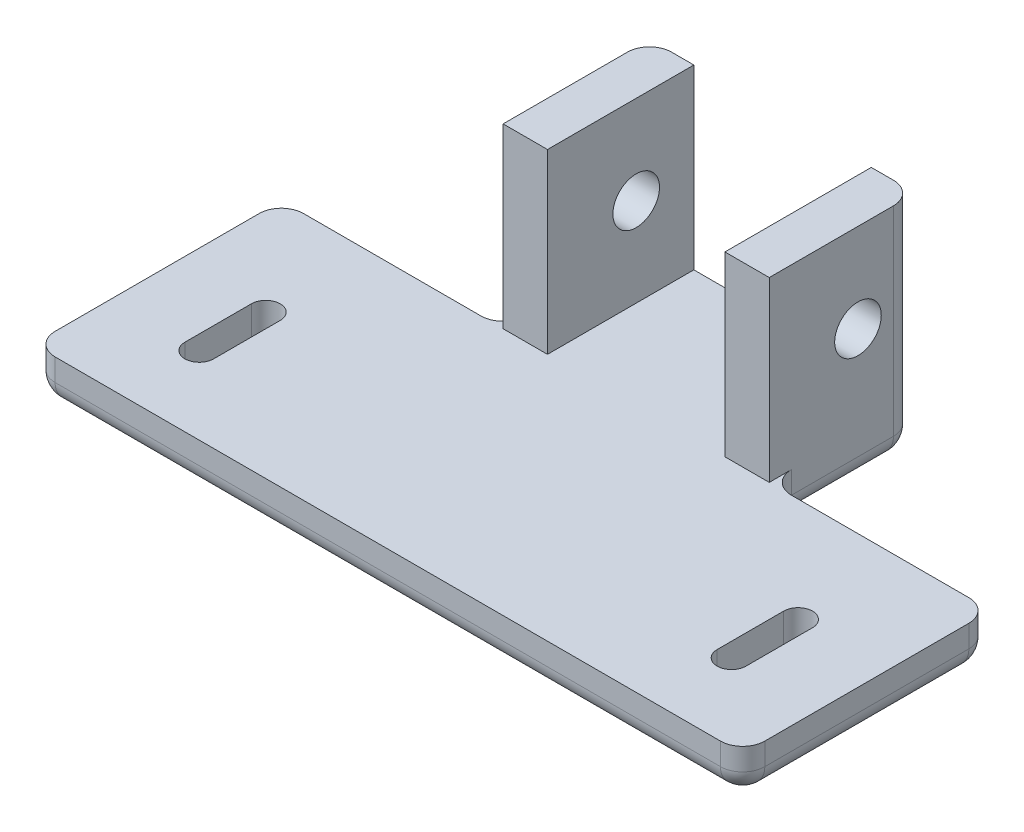
SolidWorks part; units mm, degrees
ref_plane "Front Plane" through (0, 0, 0) normal (0, 0, 1) x (1, 0, 0)
ref_plane "Top Plane" through (0, 0, 0) normal (0, 1, 0) x (1, 0, 0)
ref_plane "Right Plane" through (0, 0, 0) normal (1, 0, 0) x (0, 0, -1)
sketch "Sketch1" plane through (0, 0, 0) normal (1, 0, 0) x (0, 0, -1)
  line L0 (-10, -10) -> (6.5, -10)
  line L5 (-10, 10) -> (6.5, 10)
  line L7 (-10, -15) -> (6.5, -15)
  line L8 (6.5, 10) -> (6.5, -15)
  line L9 (-10, -10) -> (-38, -10)
  line L10 (-38, -10) -> (-38, -15)
  line L11 (-38, -15) -> (-10, -15)
  line L12 (6.5, 10) -> (10, 10) construction
  line L13 (10, 10) -> (10, -15) construction
  line L14 (10, -15) -> (6.5, -15) construction
  line L15 (-10, -10) -> (-10, 10)
  line L16 (-10, -15) -> (-10, -10)
  line L17 (-13, -10) -> (-13, -15) construction
  line L18 (-25.5, -10) -> (-25.5, -15) construction
  circle A0 centre (0, 0) radius 2.625
  point P4 (-10, 0)
  point P6 (0, 0)
  dimension "D9" = 5.25
  dimension "D1" = 20
  dimension "D2" = 10
  dimension "D3" = 20
  dimension "D4" = 5
  dimension "D5" = 3.5
  dimension "D6" = 3
  dimension "D7" = 25
  dimension "D8" = 12.5
extrude "Boss-Extrude1" add sketch "Sketch1" along normal blind 5 from offset 10 contours L15 L0 L8 L5 region at (0, 0, 9.7407)
extrude "Boss-Extrude2" add sketch "Sketch1<3>" against normal blind 5 from offset 10 separate body contours L15 L0 L8 L5 region at (0, 0, 9.7407) offset against normal yes
sketch "Sketch1<3>" plane through (0, 0, 0) normal (1, 0, 0) x (0, 0, -1) same geometry as "Sketch1"
extrude "Boss-Extrude3" add sketch "Sketch1<4>" along normal up to surface (15 mm away) and the other way up to surface (15 mm away) contours L16 L7 L8 L0 | L11 L16 L9 L10 region at (0, -12.5, 24) region at (0, -12.5, 1.75) up to face at (15, 0, -2.625) other way up to face at (-15, 0, -2.625)
sketch "Sketch1<4>" plane through (0, 0, 0) normal (1, 0, 0) x (0, 0, -1) same geometry as "Sketch1"
sketch "Sketch2" plane through (0, -10, 0) normal (0, 1, 0) x (1, 0, 0)
  line L0 (-15, -10) -> (-40, -10)
  line L1 (-40, -10) -> (-40, -38)
  line L2 (-40, -38) -> (-15, -38)
  line L3 (-15, -10) -> (-15, -38)
  line L4 (0, -1000) -> (0, 49000) construction
  line L5 (15, -10) -> (15, -38)
  line L6 (40, -38) -> (15, -38)
  line L7 (40, -10) -> (40, -38)
  line L8 (15, -10) -> (40, -10)
  line L9 (-30, -29.25) -> (-30, -21.75) construction
  line L10 (-31.625, -29.25) -> (-31.625, -21.75)
  line L11 (-28.375, -29.25) -> (-28.375, -21.75)
  line L12 (30, -29.25) -> (30, -21.75) construction
  line L13 (31.625, -29.25) -> (31.625, -21.75)
  line L14 (28.375, -29.25) -> (28.375, -21.75)
  arc A0 (-31.625, -29.25) -> (-28.375, -29.25) centre (-30, -29.25) ccw
  arc A1 (-28.375, -21.75) -> (-31.625, -21.75) centre (-30, -21.75) ccw
  arc A2 (31.625, -29.25) -> (28.375, -29.25) centre (30, -29.25) cw
  arc A3 (28.375, -21.75) -> (31.625, -21.75) centre (30, -21.75) cw
  point P6 (-30, -25.5)
  point P13 (30, -25.5)
  point P14 (-30, -25.5)
  point P24 (30, -25.5)
  line M6 (-15, -10) -> (-15, -38)
  line M8 (15, -38) -> (15, -10)
  dimension "D4" = 1.625
  dimension "D1" = 12.5
  dimension "D2" = 60
  dimension "D3" = 10
  dimension "D5" = 7.5
extrude "Boss-Extrude4" add sketch "Sketch2" against normal up to surface (5 mm away) contours L1 L2 L0 M6 | L8 L6 L7 M8 region at (-27.3776, -10, 23.9266) region at (27.3776, -10, 23.9266) up to face at (0, -15, 15.75)
fillet "Fillet1" radius 2.5 16 edges at (-27.5, -15, 10) (27.5, -15, 10) (-15, -15, 1.75) (15, -15, 1.75) (0, -15, -6.5) (15, -12.5, 10) (-15, -12.5, 10) (-15, -2.5, -6.5) (15, -2.5, -6.5) (40, -12.5, 10) (40, -12.5, 38) (-40, -12.5, 10) (-40, -12.5, 38) (-40, -15, 24) (0, -15, 38) (40, -15, 24)
equation "\"D8@Sketch1\"=\"D7@Sketch1\"/2"
